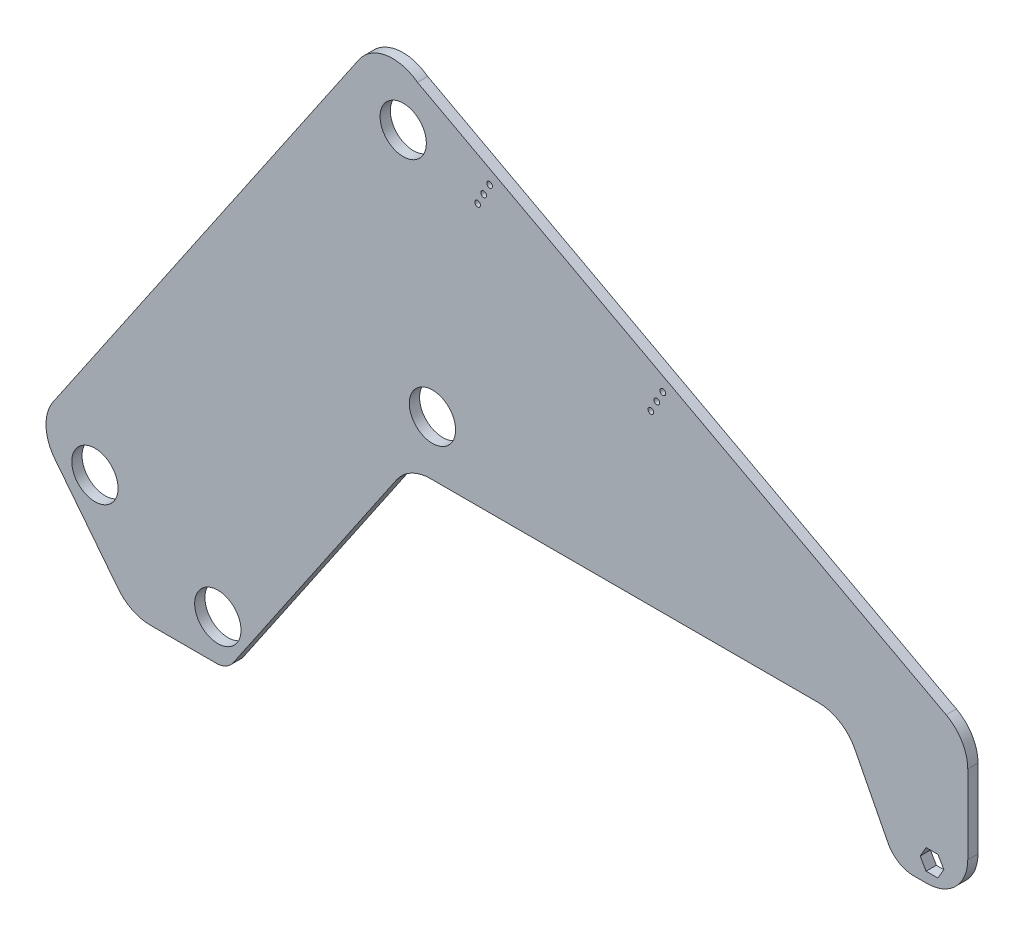
SolidWorks part; units mm, degrees
other "Markup1"
sketch "Sketch1" plane through (-441.7893, 331.8239, 6.35) normal (-0.0431, 0.0102, 0.999) x (0.9985, 0.0354, 0.0427)
sketch "Sketch2" plane through (-413.6701, 343.933, 6.35) normal (-0.0431, 0.0102, 0.999) x (0.9985, 0.0354, 0.0427)
sketch "Sketch3" plane through (-436.3774, 318.5567, 6.35) normal (-0.0431, 0.0102, 0.999) x (0.9985, 0.0354, 0.0427)
sketch "Sketch5" plane through (-436.3774, 318.5567, 6.35) normal (-0.0431, 0.0102, 0.999) x (0.9985, 0.0354, 0.0427)
sketch "Sketch7" plane through (-430.3226, 318.5567, 6.35) normal (-0.0431, 0.0102, 0.999) x (0.9985, 0.0354, 0.0427)
sketch "Sketch9" plane through (-430.3226, 318.5567, 6.35) normal (-0.0431, 0.0102, 0.999) x (0.9985, 0.0354, 0.0427)
sketch "Sketch11" plane through (-430.3226, 318.5567, 6.35) normal (-0.0431, 0.0102, 0.999) x (0.9985, 0.0354, 0.0427)
sketch "Sketch13" plane through (-430.3226, 318.5567, 6.35) normal (-0.0431, 0.0102, 0.999) x (0.9985, 0.0354, 0.0427)
sketch "Sketch15" plane through (-430.3226, 318.5567, 6.35) normal (-0.0431, 0.0102, 0.999) x (0.9985, 0.0354, 0.0427)
other "Markup2"
sketch "Sketch4" plane through (102.4721, 318.5567, 6.35) normal (0.9364, 0.1073, 0.3342) x (0.3416, -0.0598, -0.9379)
sketch "Sketch6" plane through (102.4721, 318.5567, 6.35) normal (0.9364, 0.1073, 0.3342) x (0.3416, -0.0598, -0.9379)
sketch "Sketch8" plane through (141.2086, 318.5567, 6.35) normal (0.9364, 0.1073, 0.3342) x (0.3416, -0.0598, -0.9379)
sketch "Sketch10" plane through (141.2086, 318.5567, 6.35) normal (0.9364, 0.1073, 0.3342) x (0.3416, -0.0598, -0.9379)
sketch "Sketch12" plane through (141.2086, 318.5567, 6.35) normal (0.9364, 0.1073, 0.3342) x (0.3416, -0.0598, -0.9379)
sketch "Sketch14" plane through (141.2086, 318.5567, 6.35) normal (0.9364, 0.1073, 0.3342) x (0.3416, -0.0598, -0.9379)
sketch "Sketch16" plane through (141.2086, 318.5567, 6.35) normal (0.9364, 0.1073, 0.3342) x (0.3416, -0.0598, -0.9379)
material "Lexan"
ref_plane "Front Plane" through (0, 0, 0) normal (0, 0, 1) x (1, 0, 0)
ref_plane "Top Plane" through (0, 0, 0) normal (0, 1, 0) x (1, 0, 0)
ref_plane "Right Plane" through (0, 0, 0) normal (1, 0, 0) x (0, 0, -1)
sketch "Model" plane through (0, 0, 0) normal (0, 0, 1) x (1, 0, 0)
  line L1 (-191.9011, 104.6502) -> (-112.96, 104.6502)
  line L3 (-314.2383, -55.3595) -> (-212.8994, 93.5413)
  line L4 (-236.3032, 307.4477) -> (-425.9209, 28.8361)
  line L5 (-424.8981, -1.1437) -> (-385.5815, -51.2028)
  line L13 (126.3831, 53.8502) -> (122.717, 60.2002)
  line L14 (122.717, 60.2002) -> (115.3846, 60.2002)
  line L15 (115.3846, 60.2002) -> (111.7185, 53.8502)
  line L16 (111.7185, 53.8502) -> (115.3846, 47.5002)
  line L17 (115.3846, 47.5002) -> (122.717, 47.5002)
  line L18 (122.717, 47.5002) -> (126.3831, 53.8502)
  line L19 (-365.606, -60.914) -> (-324.7375, -60.914)
  line L20 (-871.0211, -88.854) -> (370.1019, -88.854) construction
  line L22 (141.2086, 66.5502) -> (141.2086, 78.8846)
  line L27 (107.6196, 41.1502) -> (115.8086, 41.1502)
  line L28 (-399.9752, 2.586) -> (-323.7752, -35.514) construction
  line L29 (-323.7752, -35.514) -> (-190.7071, 138.5169) construction
  line L30 (-190.7071, 138.5169) -> (-208.8329, 283.4378) construction
  line L31 (-208.8329, 283.4378) -> (-399.9752, 2.586) construction
  line L32 (91.8004, 50.8135) -> (71.26, 90.8456)
  line L33 (48.6612, 104.6502) -> (-11.3966, 104.6502)
  line L34 (141.2086, 78.8846) -> (141.2086, 115.3033)
  line L35 (127.8091, 137.6897) -> (-86.3327, 252.4836)
  line L36 (-112.96, 104.6502) -> (-68.51, 104.6502)
  line L37 (-122.3008, 271.7648) -> (-85.2777, 251.9181)
  line L38 (-199.9496, 313.3896) -> (-46.986, 224.7627)
  line L39 (-46.986, 224.7627) -> (-44.2259, 229.9116)
  line L40 (-68.51, 104.6502) -> (-2.1388, 104.6502)
  line L41 (-122.3008, 271.7648) -> (-199.9496, 313.3896)
  line L42 (-51.0757, 217.1337) -> (-46.986, 224.7627)
  line L43 (-47.826, 223.1957) -> (-51.5462, 216.2559) construction
  line L44 (-199.9496, 313.3896) -> (-154.405, 282.3463)
  line L45 (-154.405, 282.3463) -> (-151.6449, 287.4952)
  line L46 (-154.405, 282.3463) -> (-156.7821, 277.912)
  line L47 (-155.2451, 280.7793) -> (-158.9652, 273.8395) construction
  arc A3 (121.2475, 59.8082) -> (121.352, 60.2002) centre (96.7586, 66.5502) ccw
  circle A9 centre (-323.7752, -35.514) radius 14.351
  circle A10 centre (-399.9752, 2.586) radius 14.351
  circle A12 centre (-190.7071, 138.5169) radius 14.351
  arc A15 (107.6196, 41.1502) -> (91.8004, 50.8135) centre (107.6196, 58.9302) cw
  arc A21 (-191.9011, 104.6502) -> (-212.8994, 93.5413) centre (-191.9011, 79.2502) ccw
  circle A22 centre (-208.8329, 283.4378) radius 14.351
  circle A24 centre (119.0508, 53.8502) radius 6.35 construction
  arc A31 (-324.7375, -60.914) -> (-314.2383, -55.3595) centre (-324.7375, -48.214) ccw
  arc A40 (114.7422, 48.6129) -> (115.0458, 48.9225) centre (96.7586, 66.5502) ccw
  arc A43 (115.8086, 41.1502) -> (141.2086, 66.5502) centre (115.8086, 66.5502) ccw
  arc A44 (-236.3032, 307.4477) -> (-199.9496, 313.3896) centre (-215.305, 293.1567) cw
  arc A45 (-365.606, -60.914) -> (-385.5815, -51.2028) centre (-365.606, -35.514) cw
  arc A46 (71.26, 90.8456) -> (48.6612, 104.6502) centre (48.6612, 79.2502) ccw
  arc A47 (141.2086, 115.3033) -> (127.8091, 137.6897) centre (115.8086, 115.3033) ccw
  arc A48 (-424.8981, -1.1437) -> (-425.9209, 28.8361) centre (-404.9226, 14.5451) cw
  circle A50 centre (-47.826, 223.1957) radius 1.778
  circle A51 centre (-51.5462, 216.2559) radius 1.778
  circle A52 centre (-55.2664, 209.3162) radius 1.778
  circle A53 centre (-155.2451, 280.7793) radius 1.778
  circle A54 centre (-158.9652, 273.8395) radius 1.778
  circle A55 centre (-162.6854, 266.8998) radius 1.778
  ellipse E0 centre (-551.1692, 173.9527) end of major axis (-591.2054, 216.0961) minor radius 17.278
  point P31 (-177.5612, 330.9695)
  point P34 (100.2935, -12.8222)
  point P43 (-377.9543, -60.914)
  point P55 (96.7586, 41.1502)
  point P59 (174.831, 53.8502)
  point P60 (-205.3388, 104.6502)
  point P64 (-436.3774, 13.472)
  dimension "D3" = 38.1
  dimension "D4" = 104.6502
  dimension "D5" = 76.2
  dimension "D6" = 44.45
  dimension "D7" = 12.7
  dimension "D8" = 28.702
  dimension "D11" = 139.7
  dimension "D12" = 27.94
  dimension "D21" = 124.238
  dimension "D13" = 12.7
  dimension "D16" = 355.6
  dimension "D23" = 25.4
  dimension "D24" = 25.4
  dimension "D26" = 25.4
  dimension "D14" = 406.4
  dimension "D20" = 254
  dimension "D29" = 25.4
  dimension "D31" = 25.4
  dimension "D25" = 88.9
  dimension "D30" = 17.78
  dimension "D32" = 25.4
  dimension "D33" = 25.4
  dimension "D34" = 176.784
  dimension "D35" = 5.842
  dimension "D37" = 3
  dimension "D38" = 7.874
  dimension "D36" = 3.556
  dimension "D41" = 3.556
  dimension "D9" = 19.05
  dimension "D10" = 146.05
  dimension "D15" = 33.8667
  dimension "D17" = 339.725
  dimension "D18" = 219.075
  dimension "D19" = 50.8
  dimension "D22" = 25.4
  dimension "D27" = 53.2168
  dimension "D28" = 12.7
  dimension "D39" = 5.842
  dimension "D40" = 55.118
  dimension "D43" = 7.874
  dimension "D42" = 3
extrude "Boss-Extrude1" add sketch "Model" along normal blind 6.35 contours A51 A50 L38 A44 L4 A48 L5 A45 L19 A31 L3 A21 L1 L36 L40 L33 A46 L32 A15 L27 A43 L22 L34 A47 L35 L39 A52 A22 A12 A10 A9 L18 L17 L16 L15 L14 L13 | L37 L41 L38 L39 L35 | L44 L45 L38 | L38 L45 L41 region at (-206.9871, 107.7659, 0) region at (-168.0319, 295.5943, 0) region at (-168.9519, 293.878, 0) region at (-89.4971, 251.8082, 0)
